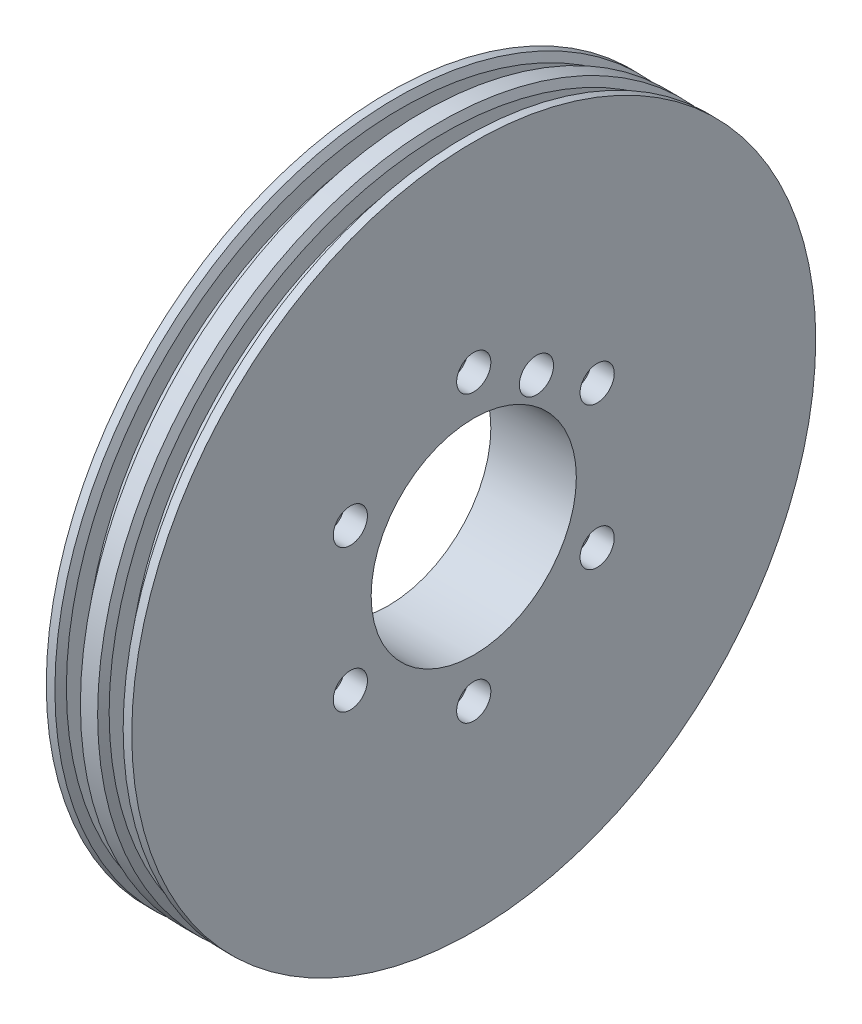
SolidWorks part; units mm, degrees
ref_plane "Front Plane" through (0, 0, 0) normal (0, 0, 1) x (1, 0, 0)
ref_plane "Top Plane" through (0, 0, 0) normal (0, 1, 0) x (1, 0, 0)
ref_plane "Right Plane" through (0, 0, 0) normal (1, 0, 0) x (0, 0, -1)
sketch "Sketch1" plane through (0, 0, 0) normal (1, 0, 0) x (0, 0, -1)
  circle A0 centre (0, 0) radius 18
  circle A1 centre (0, 0) radius 60
  dimension "D1" = 36
  dimension "D2" = 120
extrude "Boss-Extrude1" add sketch "Sketch1" along normal mid plane 15
sketch "Sketch3" plane through (7.5, 0, 0) normal (1, 0, 0) x (0, 0, -1)
  line L0 (0, 0) -> (0, 25) construction
  circle A0 centre (0, 25) radius 2
  circle A1 centre (21.6506, 12.5) radius 2
  circle A2 centre (21.6506, -12.5) radius 2
  circle A3 centre (0, -25) radius 2
  circle A4 centre (-21.6506, -12.5) radius 2
  circle A5 centre (-21.6506, 12.5) radius 2
  point P20 (0, 0)
  dimension "D1" = 25
  dimension "D2" = 6
extrude "Cut-Extrude2" cut sketch "Sketch3" against normal up to next
sketch "Sketch4" plane through (-7.5, 0, 0) normal (-1, 0, 0) x (0, 0, 1)
  circle A0 centre (0, 0) radius 33
  circle A1 centre (0, 0) radius 34.5
  circle A2 centre (0, 0) radius 31.5
  dimension "D1" = 1.5
  dimension "D2" = 1.5
extrude "Cut-Extrude3" cut sketch "Sketch4" against normal blind 3 contours A1 A0 | A0 A2 region at (-7.5, 0, -32.0666) region at (-7.5, 0, -33.5242)
sketch "Sketch5" plane through (0, 0, 0) normal (0, 0, 1) x (1, 0, 0)
  line L0 (3.75, 61.9907) -> (3.75, 57.996) construction
  line L2 (0, -60) -> (0, 60) construction
  line L3 (5.25, 55.496) -> (2.25, 55.496)
  line L4 (5.25, 55.496) -> (5.25, 58.7191)
  line L5 (5.25, 60.496) -> (2.25, 60.496)
  line L6 (2.25, 55.496) -> (2.25, 58.7191)
  line L7 (5.25, 55.496) -> (2.25, 60.496) construction
  line L8 (5.25, 60.496) -> (2.25, 55.496) construction
  line L13 (5.25, 58.7191) -> (6.2759, 60.496)
  line L14 (6.2759, 60.496) -> (5.25, 60.496)
  line L15 (1.2241, 60.496) -> (2.25, 60.496)
  line L16 (2.25, 58.7191) -> (1.2241, 60.496)
  line L17 (0, -66) -> (0, 66) construction
  line L18 (-5.25, 60.496) -> (-2.25, 55.496) construction
  line L19 (-5.25, 55.496) -> (-2.25, 60.496) construction
  line L20 (-2.25, 58.7191) -> (-1.2241, 60.496)
  line L21 (-1.2241, 60.496) -> (-2.25, 60.496)
  line L22 (-6.2759, 60.496) -> (-5.25, 60.496)
  line L23 (-5.25, 58.7191) -> (-6.2759, 60.496)
  line L24 (-2.25, 55.496) -> (-2.25, 58.7191)
  line L25 (-5.25, 60.496) -> (-2.25, 60.496)
  line L26 (-5.25, 55.496) -> (-5.25, 58.7191)
  line L27 (-5.25, 55.496) -> (-2.25, 55.496)
  dimension "D1" = 3.75
  dimension "D2" = 3
  dimension "D3" = 5
  dimension "D4" = 30
ref_axis "Axis1" through (7.5, 0, 0) along (-1, 0, 0)
revolve "Cut-Revolve2" cut sketch "Sketch5" angle 360 about axis through (7.5, 0, 0) along (-1, 0, 0)
sketch "Sketch6" plane through (7.5, 0, 0) normal (1, 0, 0) x (0, 0, -1)
  circle A8 centre (0, 25) radius 3
  circle A9 centre (21.6506, 12.5) radius 3
  circle A10 centre (21.6506, -12.5) radius 3
  circle A11 centre (0, -25) radius 3
  circle A12 centre (-21.6506, -12.5) radius 3
  circle A13 centre (-21.6506, 12.5) radius 3
  point P16 (0, 0)
extrude "Cut-Extrude4" cut sketch "Sketch6" against normal blind 4
sketch "Sketch7" plane through (-7.5, 0, 0) normal (-1, 0, 0) x (0, 0, 1)
  line L0 (0, 0) -> (-11, 19.0526) construction
  line L1 (0, 0) -> (0, 2.9604) construction
  circle A1 centre (-11, 19.0526) radius 3
  point P11 (0, 0)
  dimension "D1" = 30
  dimension "D3" = 22
extrude "Cut-Extrude5" cut sketch "Sketch7" against normal up to next
